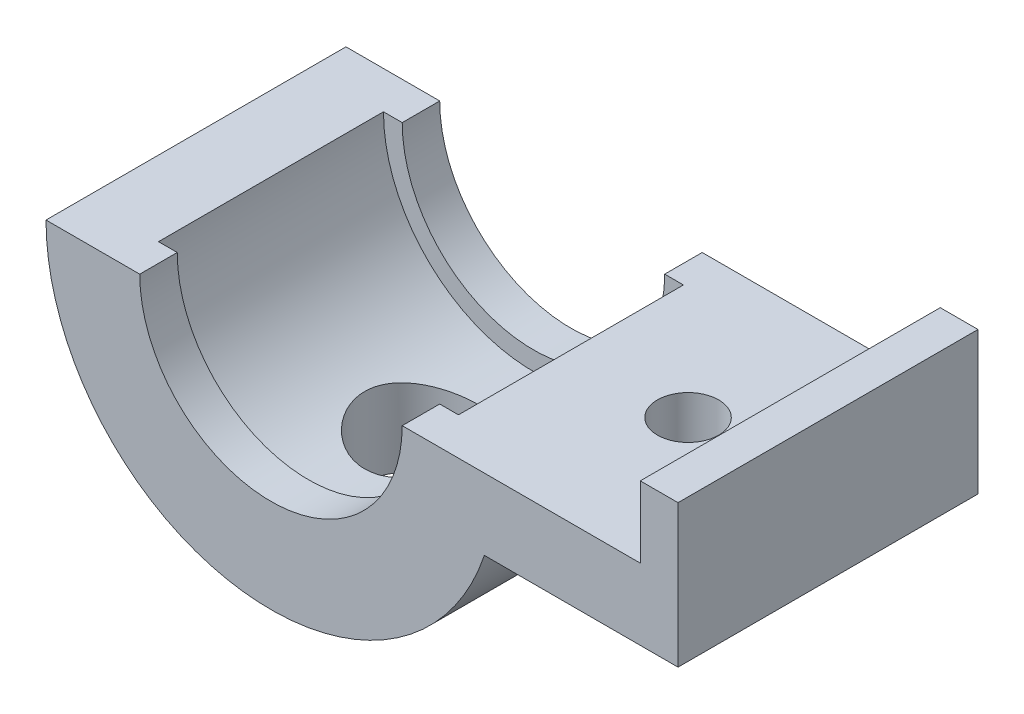
SolidWorks part; units mm, degrees
ref_plane "前视基准面" through (0, 0, 0) normal (0, 0, 1) x (1, 0, 0)
ref_plane "上视基准面" through (0, 0, 0) normal (0, 1, 0) x (1, 0, 0)
ref_plane "右视基准面" through (0, 0, 0) normal (1, 0, 0) x (0, 0, -1)
sketch "草图1" plane through (0, 0, 0) normal (0, 0, 1) x (1, 0, 0)
  line L0 (-60, 0) -> (-35, 0)
  line L1 (35, 0) -> (60, 0)
  arc A0 (-60, 0) -> (60, 0) centre (0, 0) ccw
  arc A1 (-35, 0) -> (35, 0) centre (0, 0) ccw
extrude "凸台-拉伸1" add sketch "草图1" along normal blind 40 and the other way blind 40
sketch "草图2" plane through (0, 0, 0) normal (0, 0, 1) x (1, 0, 0)
  circle A0 centre (0, 0) radius 40
extrude "切除-拉伸1" cut sketch "草图2" against normal blind 30 and the other way blind 30
sketch "草图3" plane through (0, 0, 0) normal (0, 1, 0) x (1, 0, 0)
  circle A0 centre (0, 0) radius 15
extrude "切除-拉伸2" cut sketch "草图3" against normal blind 75
sketch "草图4" plane through (0, 0, 0) normal (0, 1, 0) x (1, 0, 0)
  line L0 (60, 40) -> (60, -40) construction
  line L1 (40.6141, 40) -> (108.558, 40)
  line L3 (40.6141, -40) -> (108.558, -40)
  line L4 (108.558, 40) -> (108.558, -40)
  line L5 (40.6141, 15.9693) -> (108.558, -40) construction
  line L6 (40.6141, -15.9693) -> (108.558, 40) construction
  line L7 (40.6141, 40) -> (40.6141, -40)
  point P0 (60, 0)
extrude "凸台-拉伸2" add sketch "草图4" against normal blind 19
sketch "草图5" plane through (0, 0, 0) normal (0, 1, 0) x (1, 0, 0)
  line L0 (108.558, -40) -> (35, -40) construction
  line L1 (108.558, 40) -> (98.4889, 40)
  line L2 (108.558, 40) -> (108.558, -40)
  line L3 (108.558, -40) -> (98.4889, -40)
  line L4 (98.4889, 40) -> (98.4889, -40)
extrude "凸台-拉伸3" add sketch "草图5" along normal blind 19
sketch "草图6" plane through (0, 0, 0) normal (0, 1, 0) x (1, 0, 0)
  circle A0 centre (71.2326, 0) radius 8.163
extrude "切除-拉伸3" cut sketch "草图6" against normal blind 34 contours A0
